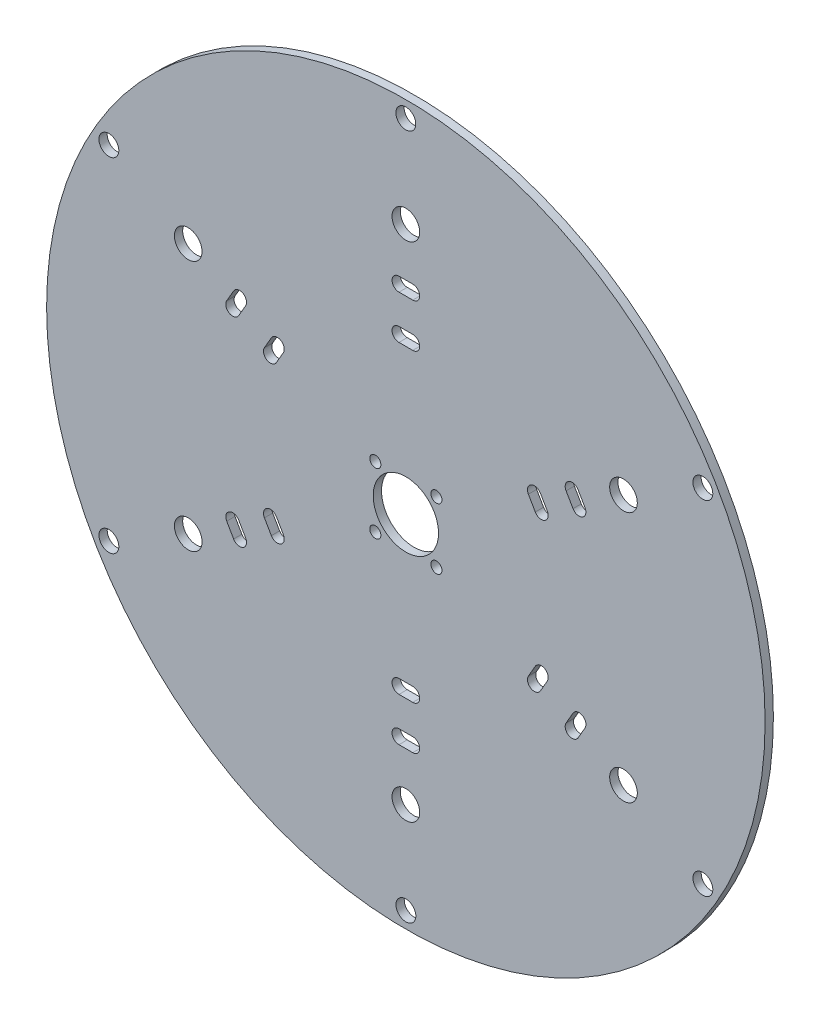
SolidWorks part; units mm, degrees
ref_plane "Front Plane" through (0, 0, 0) normal (0, 0, 1) x (1, 0, 0)
ref_plane "Top Plane" through (0, 0, 0) normal (0, 1, 0) x (1, 0, 0)
ref_plane "Right Plane" through (0, 0, 0) normal (1, 0, 0) x (0, 0, -1)
sketch "Sketch1" plane through (0, 0, 0) normal (0, 0, 1) x (1, 0, 0)
  circle A0 centre (0, 0) radius 165
extrude "Boss-Extrude1" add sketch "Sketch1" along normal blind 3.8 contours A0
sketch "Sketch2" plane through (0, 0, 3.8) normal (0, 0, 1) x (1, 0, 0)
  circle A0 centre (0, 0) radius 15
extrude "Cut-Extrude1" cut sketch "Sketch2" against normal blind 13.716 contours A0
sketch "Sketch3" plane through (0, 0, 3.8) normal (0, 0, 1) x (1, 0, 0)
  line L1 (34.8, 34.8) -> (-34.8, 34.8)
  line L2 (34.8, 34.8) -> (34.8, -34.8)
  line L3 (34.8, -34.8) -> (-34.8, -34.8)
  line L4 (-34.8, 34.8) -> (-34.8, -34.8)
  line L5 (34.8, 34.8) -> (-34.8, -34.8) construction
  line L6 (34.8, -34.8) -> (-34.8, 34.8) construction
  point P0 (0, 0)
sketch "Sketch6" plane through (0, 0, 3.8) normal (0, 0, 1) x (1, 0, 0)
  circle A0 centre (0, 0) radius 105
sketch "Sketch7" plane through (0, 0, 3.8) normal (0, 0, 1) x (1, 0, 0)
  line L1 (0, 105) -> (-90.9327, 52.5)
  line L2 (-90.9327, 52.5) -> (-90.9327, -52.5)
  line L3 (-90.9327, -52.5) -> (0, -105)
  line L4 (0, -105) -> (90.9327, -52.5)
  line L5 (90.9327, -52.5) -> (90.9327, 52.5)
  line L6 (90.9327, 52.5) -> (0, 105)
  circle A0 centre (0, 0) radius 90.9327 construction
  circle A1 centre (0, 0) radius 105 construction
sketch "Sketch8" plane through (0, 0, 3.8) normal (0, 0, 1) x (1, 0, 0)
  line L0 (0, 0) -> (0, 165)
  circle A0 centre (0, 0) radius 165 construction
sketch "Sketch9" plane through (0, 0, 0) normal (0, 0, -1) x (-1, 0, 0)
  circle A0 centre (0, 105) radius 3.175
  circle A1 centre (90.9327, 52.5) radius 3.175
  circle A2 centre (90.9327, -52.5) radius 3.175
  circle A3 centre (0, -105) radius 3.175
  circle A4 centre (-90.9327, -52.5) radius 3.175
  circle A5 centre (-90.9327, 52.5) radius 3.175
sketch "Sketch11" plane through (0, 0, 3.8) normal (0, 0, 1) x (1, 0, 0)
  line L1 (-0.0168, 157.5) -> (-136.4074, 78.7355)
  line L2 (-136.4074, 78.7355) -> (-136.3906, -78.7645)
  line L3 (-136.3906, -78.7645) -> (0.0168, -157.5)
  line L4 (0.0168, -157.5) -> (136.4074, -78.7355)
  line L5 (136.4074, -78.7355) -> (136.3906, 78.7645)
  line L6 (136.3906, 78.7645) -> (-0.0168, 157.5)
  circle A0 centre (0, 0) radius 136.399 construction
sketch "Sketch12" plane through (0, 0, 3.8) normal (0, 0, 1) x (1, 0, 0)
  circle A0 centre (-0.0168, 157.5) radius 3.97
  circle A1 centre (136.3906, 78.7645) radius 3.97
  circle A2 centre (136.4074, -78.7355) radius 3.97
  circle A3 centre (-136.3906, -78.7645) radius 3.97
  circle A4 centre (-136.4074, 78.7355) radius 3.97
  circle A5 centre (0.0168, -157.5) radius 3.97
sketch "Sketch17" plane through (0, 0, 3.8) normal (0, 0, 1) x (1, 0, 0)
  circle A0 centre (0, 105) radius 50
  circle A1 centre (90.9327, 52.5) radius 50
  circle A2 centre (90.9327, -52.5) radius 50
  circle A3 centre (-90.9327, 52.5) radius 50
  circle A4 centre (-90.9327, -52.5) radius 50
  circle A5 centre (0, -105) radius 50
sketch "Sketch32" plane through (0, 0, 0) normal (0, 0, -1) x (-1, 0, 0)
  line L0 (-82.5, 142.8942) -> (82.5, -142.8942)
  line L1 (82.5, -142.8942) -> (165, 0)
  line L2 (165, 0) -> (82.5, 142.8942)
  line L3 (82.5, 142.8942) -> (-82.5, 142.8942)
  line L4 (-82.5, 142.8942) -> (-165, 0)
  line L5 (-165, 0) -> (-82.5, -142.8942)
  line L6 (-82.5, -142.8942) -> (82.5, -142.8942)
  line L7 (82.5, 142.8942) -> (-82.5, -142.8942)
  line L8 (-165, 0) -> (165, 0)
  circle A0 centre (0, 0) radius 142.8942 construction
  circle A1 centre (0, 0) radius 165 construction
sketch "Sketch38" plane through (0, 0, 0) normal (0, 0, -1) x (-1, 0, 0)
  line L0 (-121.8458, 44.2168) -> (-99.2158, 83.4132)
  line L1 (-121.8458, 44.2168) -> (-82.6495, 21.5868)
  line L2 (-99.2158, 83.4132) -> (-60.0195, 60.7832)
  line L3 (-82.6495, 21.5868) -> (-60.0195, 60.7832)
  line L4 (-121.8458, 44.2168) -> (-60.0195, 60.7832) construction
  line L5 (-99.2158, 83.4132) -> (-82.6495, 21.5868) construction
  line L6 (-22.63, 82.37) -> (22.63, 82.37)
  line L7 (-22.63, 82.37) -> (-22.63, 127.63)
  line L8 (22.63, 82.37) -> (22.63, 127.63)
  line L9 (-22.63, 127.63) -> (22.63, 127.63)
  line L10 (-22.63, 82.37) -> (22.63, 127.63) construction
  line L11 (22.63, 82.37) -> (-22.63, 127.63) construction
  line L12 (60.0195, 60.7832) -> (82.6495, 21.5868)
  line L13 (60.0195, 60.7832) -> (99.2158, 83.4132)
  line L14 (82.6495, 21.5868) -> (121.8458, 44.2168)
  line L15 (99.2158, 83.4132) -> (121.8458, 44.2168)
  line L16 (60.0195, 60.7832) -> (121.8458, 44.2168) construction
  line L17 (82.6495, 21.5868) -> (99.2158, 83.4132) construction
  line L18 (60.0195, -60.7832) -> (99.2158, -83.4132)
  line L19 (60.0195, -60.7832) -> (82.6495, -21.5868)
  line L20 (99.2158, -83.4132) -> (121.8458, -44.2168)
  line L21 (82.6495, -21.5868) -> (121.8458, -44.2168)
  line L22 (60.0195, -60.7832) -> (121.8458, -44.2168) construction
  line L23 (99.2158, -83.4132) -> (82.6495, -21.5868) construction
  line L24 (-22.63, -127.63) -> (22.63, -127.63)
  line L25 (-22.63, -127.63) -> (-22.63, -82.37)
  line L26 (22.63, -127.63) -> (22.63, -82.37)
  line L27 (-22.63, -82.37) -> (22.63, -82.37)
  line L28 (-22.63, -127.63) -> (22.63, -82.37) construction
  line L29 (22.63, -127.63) -> (-22.63, -82.37) construction
  line L30 (-121.8458, -44.2168) -> (-99.2158, -83.4132)
  line L31 (-121.8458, -44.2168) -> (-82.6495, -21.5868)
  line L32 (-99.2158, -83.4132) -> (-60.0195, -60.7832)
  line L33 (-82.6495, -21.5868) -> (-60.0195, -60.7832)
  line L34 (-121.8458, -44.2168) -> (-60.0195, -60.7832) construction
  line L35 (-99.2158, -83.4132) -> (-82.6495, -21.5868) construction
  point P1 (-90.9327, 52.5)
  point P2 (0, 105)
  point P3 (90.9327, 52.5)
  point P8 (90.9327, -52.5)
  point P13 (0, -105)
  point P18 (-90.9327, -52.5)
sketch "Sketch40" plane through (0, 0, 16.872) normal (0, 0, 1) x (1, 0, 0)
  circle A0 centre (0, 0) radius 157.5
sketch "Sketch51" plane through (0, 0, 0) normal (0, 0, -1) x (-1, 0, 0)
  line L0 (-136.4074, -78.7355) -> (136.4074, 78.7355)
  line L1 (0, 165) -> (0, -165)
  line L2 (-136.3906, 78.7645) -> (136.3906, -78.7645)
  circle A0 centre (0, 0) radius 70
  circle A1 centre (0, 0) radius 90
  circle A2 centre (0, 0) radius 165 construction
  circle A3 centre (0, 0) radius 105
  circle A4 centre (0, 0) radius 115.41
sketch "Sketch48" plane through (0, 0, 0) normal (0, 0, -1) x (-1, 0, 0)
  line L2 (0, 0) -> (45.4663, -78.75)
  line L3 (0, 0) -> (-45.4663, -78.75)
  line L4 (0, 0) -> (-90.9327, 0)
  line L5 (0, 0) -> (-45.4663, 78.75)
  line L6 (0, 0) -> (45.4663, 78.75)
  line L7 (0, 0) -> (90.9327, 0)
sketch "Sketch53" plane through (0, 0, 0) normal (0, 0, -1) x (-1, 0, 0)
  line L5 (-14.0317, 14.0317) -> (-14.0317, -14.0317)
  line L7 (-14.0317, 14.0317) -> (14.0317, 14.0317)
  line L8 (-14.0317, -14.0317) -> (14.0317, -14.0317)
  line L9 (14.0317, 14.0317) -> (14.0317, -14.0317)
  line L10 (-34.8, -34.8) -> (34.8, 34.8) construction
  line L11 (-34.8, 34.8) -> (34.8, 34.8) construction
  circle A0 centre (0, 0) radius 19.8437
sketch "Sketch49" plane through (0, 0, 0) normal (0, 0, -1) x (-1, 0, 0)
  line L0 (0, 165) -> (0, -165) construction
  line L1 (-136.4074, -78.7355) -> (136.4074, 78.7355) construction
  line L2 (-136.3906, 78.7645) -> (136.3906, -78.7645) construction
  circle A0 centre (-99.9541, -57.6943) radius 6.35
  circle A1 centre (0, -115.41) radius 6.35
  circle A2 centre (99.9418, -57.7157) radius 6.35
  circle A3 centre (99.9541, 57.6943) radius 6.35
  circle A4 centre (0, 115.41) radius 6.35
  circle A5 centre (-99.9418, 57.7157) radius 6.35
  circle A7 centre (0, 0) radius 115.41 construction
sketch "Sketch52" plane through (0, 0, 0) normal (0, 0, -1) x (-1, 0, 0)
  line L0 (-3.2528, -69.9908) -> (3.0937, -69.9908) construction
  line L1 (-3.2528, -66.8224) -> (3.0937, -66.8224)
  line L2 (-3.2528, -73.1592) -> (3.0937, -73.1592)
  line L3 (-3.3081, -89.9884) -> (3.1081, -89.9956) construction
  line L6 (-3.3046, -86.8337) -> (3.1116, -86.8409)
  line L9 (58.9941, -37.8163) -> (62.1697, -32.3173) construction
  line L10 (56.2464, -36.2294) -> (59.4219, -30.7305)
  line L11 (61.7419, -39.4031) -> (64.9175, -33.9041)
  line L12 (76.3021, -47.8319) -> (79.4777, -42.333) construction
  line L13 (73.552, -46.2437) -> (76.7276, -40.7448)
  line L14 (79.0523, -49.4201) -> (82.2279, -43.9212)
  line L15 (62.2441, 32.177) -> (59.0681, 37.6793) construction
  line L16 (59.4895, 30.587) -> (56.3135, 36.0894)
  line L17 (64.9987, 33.7669) -> (61.8227, 39.2693)
  line L21 (79.5775, 42.1588) -> (76.4015, 47.6612) construction
  line L22 (76.8335, 40.5749) -> (73.6575, 46.0773)
  line L23 (82.3216, 43.7427) -> (79.1456, 49.2451)
  line L24 (-3.075, 89.9999) -> (3.275, 89.9999) construction
  line L25 (-3.075, 93.1745) -> (3.275, 93.1745)
  line L26 (-3.075, 86.8254) -> (3.275, 86.8254)
  line L27 (-3.0972, 69.9943) -> (3.2528, 69.9943) construction
  line L28 (-3.0972, 73.1689) -> (3.2528, 73.1689)
  line L29 (-3.0972, 66.8198) -> (3.2528, 66.8198)
  line L30 (-76.3012, 47.8342) -> (-79.4768, 42.3352) construction
  line L31 (-73.5517, 46.2464) -> (-76.7273, 40.7474)
  line L32 (-79.0507, 49.422) -> (-82.2263, 43.923)
  line L33 (-58.987, 37.8121) -> (-62.1625, 32.3132) construction
  line L34 (-56.2375, 36.2243) -> (-59.413, 30.7253)
  line L35 (-61.7364, 39.3999) -> (-64.912, 33.901)
  line L36 (-76.3855, -47.7035) -> (-79.599, -42.1232) construction
  line L39 (-59.0381, -37.7175) -> (-62.2589, -32.1375) construction
  line L40 (-61.796, -39.3094) -> (-65.0168, -33.7294)
  line L41 (-56.2802, -36.1256) -> (-59.501, -30.5456)
  line L42 (-136.4074, -78.7355) -> (136.4074, 78.7355) construction
  line L43 (0, 165) -> (0, -165) construction
  line L44 (-79.1406, -49.2901) -> (-82.354, -43.7097)
  line L45 (-73.6304, -46.117) -> (-76.8439, -40.5367)
  line L46 (-3.3116, -93.1432) -> (3.1046, -93.1503)
  line L47 (-136.3906, 78.7645) -> (136.3906, -78.7645) construction
  arc A12 (-3.2528, -66.8224) -> (-3.2528, -73.1592) centre (-3.2528, -69.9908) ccw
  arc A13 (3.0937, -73.1592) -> (3.0937, -66.8224) centre (3.0937, -69.9908) ccw
  arc A18 (56.2464, -36.2294) -> (61.7419, -39.4031) centre (58.9941, -37.8163) ccw
  arc A19 (64.9175, -33.9041) -> (59.4219, -30.7305) centre (62.1697, -32.3173) ccw
  arc A20 (73.552, -46.2437) -> (79.0523, -49.4201) centre (76.3021, -47.8319) ccw
  arc A21 (82.2279, -43.9212) -> (76.7276, -40.7448) centre (79.4777, -42.333) ccw
  arc A22 (59.4895, 30.587) -> (64.9987, 33.7669) centre (62.2441, 32.177) ccw
  arc A23 (61.8227, 39.2693) -> (56.3135, 36.0894) centre (59.0681, 37.6793) ccw
  arc A26 (76.8335, 40.5749) -> (82.3216, 43.7427) centre (79.5775, 42.1588) ccw
  arc A27 (79.1456, 49.2451) -> (73.6575, 46.0773) centre (76.4015, 47.6612) ccw
  arc A28 (-3.075, 93.1745) -> (-3.075, 86.8254) centre (-3.075, 89.9999) ccw
  arc A29 (3.275, 86.8254) -> (3.275, 93.1745) centre (3.275, 89.9999) ccw
  arc A30 (-3.0972, 73.1689) -> (-3.0972, 66.8198) centre (-3.0972, 69.9943) ccw
  arc A31 (3.2528, 66.8198) -> (3.2528, 73.1689) centre (3.2528, 69.9943) ccw
  arc A32 (-73.5517, 46.2464) -> (-79.0507, 49.422) centre (-76.3012, 47.8342) ccw
  arc A33 (-82.2263, 43.923) -> (-76.7273, 40.7474) centre (-79.4768, 42.3352) ccw
  arc A34 (-56.2375, 36.2243) -> (-61.7364, 39.3999) centre (-58.987, 37.8121) ccw
  arc A35 (-64.912, 33.901) -> (-59.413, 30.7253) centre (-62.1625, 32.3132) ccw
  arc A38 (-61.796, -39.3094) -> (-56.2802, -36.1256) centre (-59.0381, -37.7175) ccw
  arc A39 (-59.501, -30.5456) -> (-65.0168, -33.7294) centre (-62.2589, -32.1375) ccw
  arc A40 (-79.1406, -49.2901) -> (-73.6304, -46.117) centre (-76.3855, -47.7035) ccw
  arc A41 (-76.8439, -40.5367) -> (-82.354, -43.7097) centre (-79.599, -42.1232) ccw
  arc A42 (-3.3046, -86.8337) -> (-3.3116, -93.1432) centre (-3.3081, -89.9884) ccw
  arc A43 (3.1046, -93.1503) -> (3.1116, -86.8409) centre (3.1081, -89.9956) ccw
  point P26 (-0.0795, -69.9908)
  point P34 (-0.1, -89.992)
  point P40 (60.5819, -35.0668)
  point P54 (77.8899, -45.0825)
  point P61 (60.6561, 34.9282)
  point P75 (77.9895, 44.91)
  point P82 (0.1, 89.9999)
  point P89 (0.0778, 69.9943)
  point P96 (-77.889, 45.0847)
  point P103 (-60.5747, 35.0626)
  point P110 (-77.9922, -44.9134)
  point P117 (-60.6485, -34.9275)
sketch "Sketch47" plane through (0, 0, 0) normal (0, 0, -1) x (-1, 0, 0)
  circle A0 centre (-14.0317, -14.0317) radius 3.175
  circle A1 centre (-14.0317, 14.0317) radius 3.175
  circle A2 centre (14.0317, 14.0317) radius 3.175
  circle A3 centre (14.0317, -14.0317) radius 3.175
sketch "Sketch13" plane through (0, 0, 3.8) normal (0, 0, 1) x (1, 0, 0)
  circle A0 centre (0, 105) radius 45.5
  circle A1 centre (90.9327, 52.5) radius 45.5
  circle A2 centre (90.9327, -52.5) radius 45.5
  circle A3 centre (-90.9327, 52.5) radius 45.5
  circle A4 centre (-90.9327, -52.5) radius 45.5
  circle A5 centre (0, -105) radius 45.5
hole_wizard "23/64 (0.35938) Diameter Hole1" positions "Sketch58" profile "Sketch59" hole size "23/64" standard "ANSI Inch" end condition through all
sketch "Sketch58" plane through (0, 0, 0) normal (0, 0, -1) x (-1, 0, 0)
  point P0 (-136.3906, 78.7645)
  point P3 (-136.4074, -78.7355)
  point P6 (-0.0168, -157.5)
  point P9 (136.3906, -78.7645)
  point P12 (136.4074, 78.7355)
  point P15 (0.0168, 157.5)
sketch "Sketch59" plane through (136.3906, 78.7645, 0) normal (1, 0, 0) x (0, 1, 0)
  line L0 (0, 0) -> (0, 3.8)
  line L1 (0, 3.8) -> (4.5641, 3.8)
  line L2 (4.5641, 3.8) -> (4.5641, 0)
  line L5 (4.5641, 0) -> (0, 0)
  line L11 (0, -6.35) -> (0, 107.95) construction
  dimension "Thru Hole Dia." = 9.1283
  dimension "Thru Hole Depth" = 3.8
hole_wizard "1/2 (0.5) Diameter Hole2" positions "Sketch63" profile "Sketch64" hole size "1/2" standard "ANSI Inch" end condition through all
sketch "Sketch63" plane through (0, 0, 3.8) normal (0, 0, 1) x (1, 0, 0)
  point P0 (0, -115.41)
  point P3 (99.9541, -57.6943)
  point P6 (99.9418, 57.7157)
  point P9 (0, 115.41)
  point P12 (-99.9541, 57.6943)
  point P15 (-99.9418, -57.7157)
sketch "Sketch64" plane through (0, -115.41, 3.8) normal (1, 0, 0) x (0, -1, 0)
  line L0 (0, 0) -> (0, 3.8)
  line L1 (0, 3.8) -> (6.35, 3.8)
  line L2 (6.35, 3.8) -> (6.35, 0)
  line L5 (6.35, 0) -> (0, 0)
  line L11 (0, -6.35) -> (0, 107.95) construction
  dimension "Thru Hole Dia." = 12.7
  dimension "Thru Hole Depth" = 3.8
hole_wizard "1/4 (0.25) Diameter Slot4" positions "Sketch67" profile "Sketch66" size "1/4" standard "ANSI Inch" slot yes end condition through all
sketch "Sketch67" plane through (0, 0, 3.8) normal (0, 0, 1) x (1, 0, 0)
  line L0 (0, 165) -> (0, -165) construction
  line L1 (-6.35, -90) -> (6.35, -90) construction
  circle A0 centre (0, 0) radius 90 construction
  circle A1 centre (0, 0) radius 70 construction
  point P0 (0, -90)
  point P8 (0, -70)
  point P12 (0, 70)
  point P14 (0, 90)
  dimension "D1" = 12.7
sketch "Sketch66" plane through (0, -90, 3.8) normal (1, 0, 0) x (0, -1, 0)
  line L0 (0, 0) -> (0, 3.8)
  line L1 (0, 3.8) -> (3.175, 3.8)
  line L2 (3.175, 3.8) -> (3.175, 0)
  line L5 (3.175, 0) -> (0, 0)
  line L11 (0, -6.35) -> (0, 107.95) construction
  dimension "Thru Hole Dia." = 6.35
  dimension "Thru Hole Depth" = 3.8
hole_wizard "1/4 (0.25) Diameter Slot2" positions "Sketch68" profile "Sketch69" size "1/4" standard "ANSI Inch" slot yes end condition through all
sketch "Sketch68" plane through (0, 0, 3.8) normal (0, 0, 1) x (1, 0, 0)
  line L0 (136.3906, 78.7645) -> (-136.3906, -78.7645) construction
  line L1 (74.756, 50.5038) -> (81.1071, 39.506) construction
  point P0 (77.9315, 45.0049)
  point P16 (60.6134, 35.0038)
  point P18 (-77.9314, -45.0048)
  point P20 (-60.6135, -35.0038)
  dimension "D1" = 12.7
sketch "Sketch69" plane through (77.9315, 45.0049, 3.8) normal (1, 0, 0) x (0, -1, 0)
  line L0 (0, 0) -> (0, 3.8)
  line L1 (0, 3.8) -> (3.175, 3.8)
  line L2 (3.175, 3.8) -> (3.175, 0)
  line L5 (3.175, 0) -> (0, 0)
  line L11 (0, -6.35) -> (0, 107.95) construction
  dimension "Thru Hole Dia." = 6.35
  dimension "Thru Hole Depth" = 3.8
hole_wizard "1/4 (0.25) Diameter Slot3" positions "Sketch70" profile "Sketch71" size "1/4" standard "ANSI Inch" slot yes end condition through all
sketch "Sketch70" plane through (0, 0, 3.8) normal (0, 0, 1) x (1, 0, 0)
  line L0 (136.4074, -78.7355) -> (-136.4074, 78.7355) construction
  line L1 (74.7667, -50.4878) -> (81.1155, -39.4886) construction
  point P0 (77.9411, -44.9882)
  point P8 (60.6209, -34.9909)
  point P10 (-77.9411, 44.9882)
  point P12 (-60.6209, 34.9909)
  dimension "D1" = 12.7
sketch "Sketch71" plane through (77.9411, -44.9882, 3.8) normal (1, 0, 0) x (0, -1, 0)
  line L0 (0, 0) -> (0, 3.8)
  line L1 (0, 3.8) -> (3.175, 3.8)
  line L2 (3.175, 3.8) -> (3.175, 0)
  line L5 (3.175, 0) -> (0, 0)
  line L11 (0, -6.35) -> (0, 107.95) construction
  dimension "Thru Hole Dia." = 6.35
  dimension "Thru Hole Depth" = 3.8
hole_wizard "1/4-20 Tapped Hole1" positions "Sketch72" profile "Sketch73" tap size "1/4-20" standard "ANSI Inch" end condition up to next
sketch "Sketch72" plane through (0, 0, 3.8) normal (0, 0, 1) x (1, 0, 0)
  point P0 (-14.0317, 14.0317)
  point P3 (14.0317, 14.0317)
  point P6 (-14.0317, -14.0317)
  point P9 (14.0317, -14.0317)
sketch "Sketch73" plane through (-14.0317, 14.0317, 3.8) normal (1, 0, 0) x (0, -1, 0)
  line L0 (0, 0) -> (0, 3.8)
  line L1 (0, 3.8) -> (2.5527, 3.8)
  line L2 (2.5527, 3.8) -> (2.5527, 0)
  line L5 (2.5527, 0) -> (0, 0)
  line L11 (0, -6.35) -> (0, 107.95) construction
  dimension "Thru Tap Drill Dia." = 5.1054
  dimension "Thru Tap Drill Depth" = 3.8
cosmetic thread "Hole Thread1" parameters "D2"=6.35
cosmetic thread "Hole Thread2" parameters "D2"=6.35
cosmetic thread "Hole Thread3" parameters "D2"=6.35
cosmetic thread "Hole Thread4" parameters "D2"=6.35
